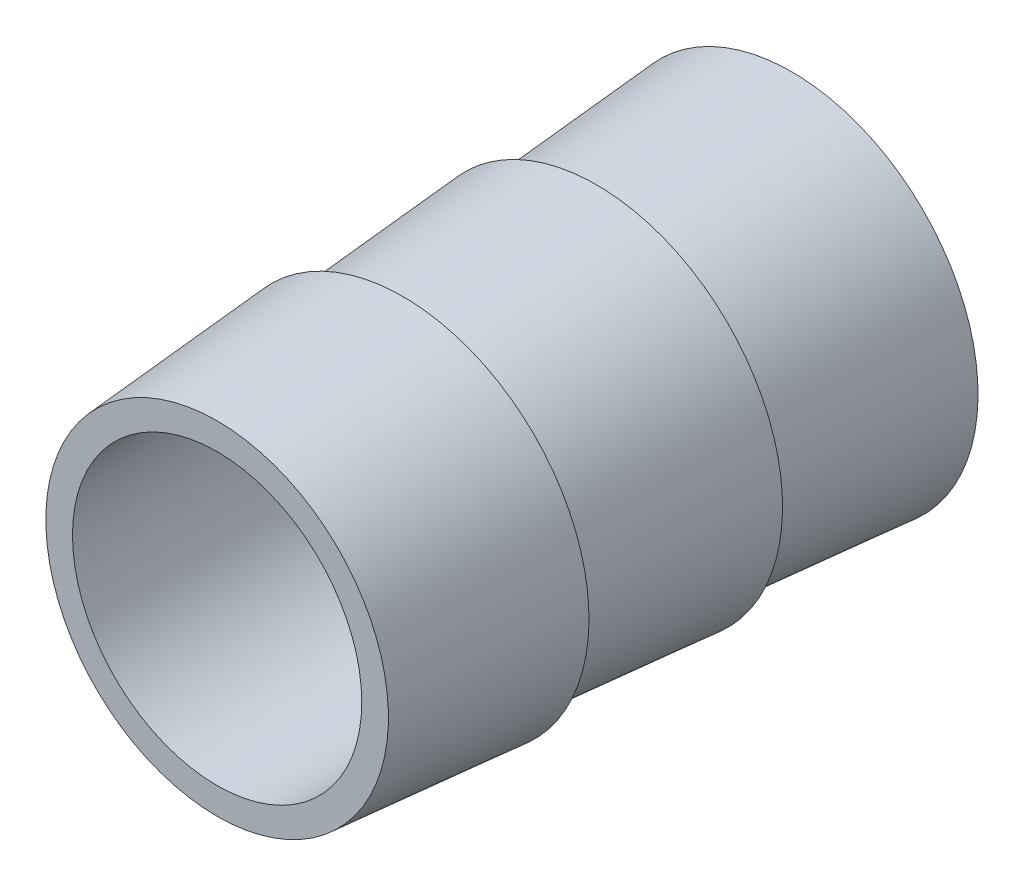
SolidWorks part; units mm, degrees
ref_plane "Front Plane" through (0, 0, 0) normal (0, 0, 1) x (1, 0, 0)
ref_plane "Top Plane" through (0, 0, 0) normal (0, 1, 0) x (1, 0, 0)
ref_plane "Right Plane" through (0, 0, 0) normal (1, 0, 0) x (0, 0, -1)
sketch "Sketch2" plane through (0, 0, 0) normal (1, 0, 0) x (0, 0, -1)
  line L0 (-0.5417, -1.2698) -> (6.8523, -1.2698)
  line L4 (-4.0009, 0.9812) -> (-0.5417, 1.2671) construction
  line L5 (-0.5417, 1.2671) -> (-0.5417, 1.975)
  line L7 (3.1381, 1.2671) -> (3.1381, 1.975)
  line L9 (6.8523, 1.2698) -> (6.8523, -1.2698)
  line L10 (-4.0009, 0.9812) -> (-4.0749, 0.9751)
  line L13 (-4.0749, 0.9751) -> (-4.0749, -1.2698)
  line L14 (-0.5417, 0.975) -> (-0.5417, -1.2698) construction
  line L15 (-0.5417, -1.2698) -> (-4.0749, -1.2698)
  line L16 (6.8523, 1.2698) -> (3.1381, 0.975) construction
  line L17 (3.1381, 1.2671) -> (-0.5417, 0.975) construction
  line L18 (3.1381, 1.2671) -> (3.1381, 2.2671)
  line L19 (3.1381, 2.2671) -> (-0.5417, 1.975)
  line L21 (6.8523, 1.2698) -> (6.8523, 2.2698)
  line L22 (6.8523, 2.2698) -> (3.1381, 1.975)
  line L23 (3.1381, 1.975) -> (3.1381, 0.975) construction
  line L24 (-0.5417, 1.2671) -> (-0.5417, 1.7692) construction
  line L25 (-0.5417, 1.2671) -> (-0.5417, 0.975)
  line L26 (-4.0749, 0.9751) -> (-4.0749, 1.9867)
  line L27 (-0.5417, 1.2671) -> (-0.5417, 2.2671)
  line L28 (-0.5417, 2.2671) -> (-4.0749, 1.9867)
  point P4 (0, 0)
  dimension "D1" = 1
  dimension "D2" = 1
  dimension "D3" = 1
revolve "Revolve2" add sketch "Sketch2" angle 360 about L0 region at (0, 0.4278, -1.413)
sketch "Sketch7" plane through (0, 0, -6.8523) normal (0, 0, -1) x (-1, 0, 0)
  line L0 (0, 2.2698) -> (0, -4.8095) construction
  circle A0 centre (0, -1.2698) radius 3.5397 construction
  circle A1 centre (0, -1.2698) radius 2.75
  dimension "D1" = 5.5
extrude "Cut-Extrude3" cut sketch "Sketch7" against normal through all
